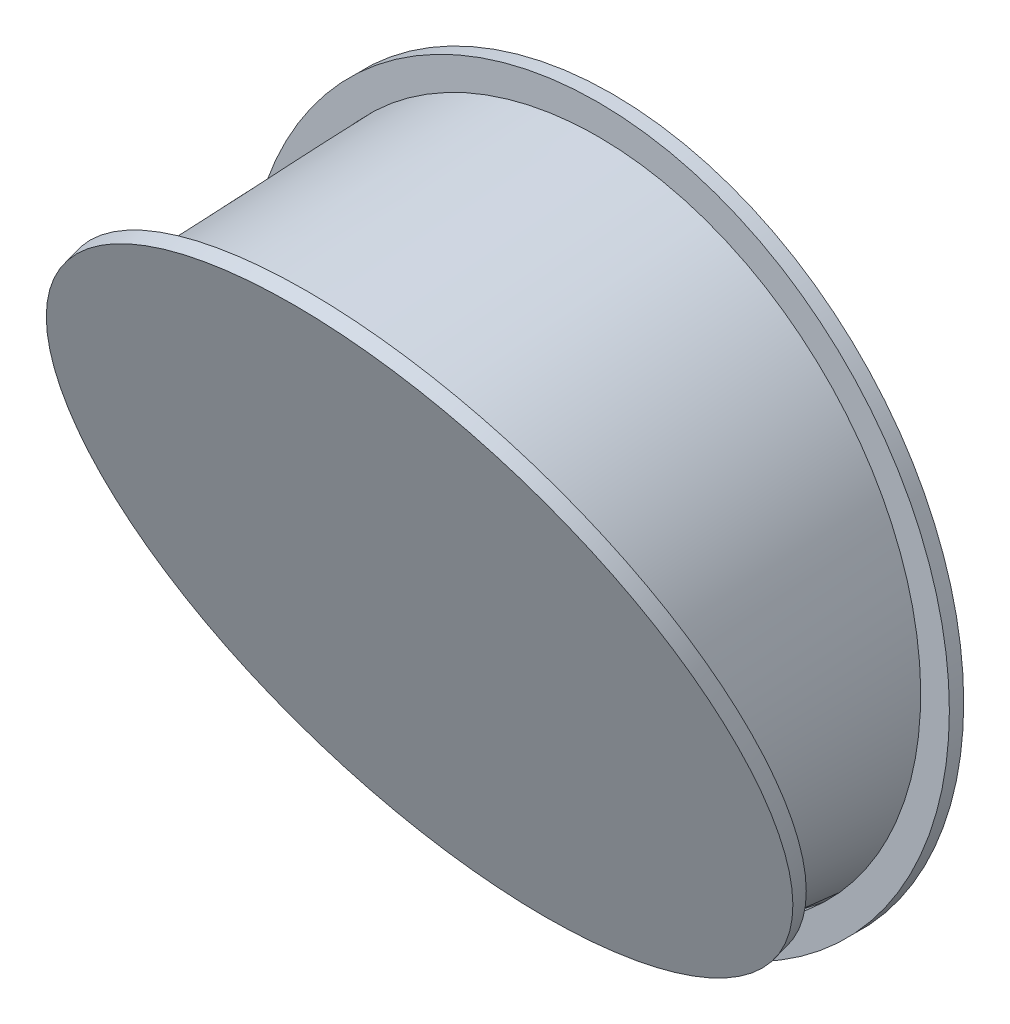
SolidWorks part; units mm, degrees
ref_plane "Front Plane" through (0, 0, 0) normal (0, 0, 1) x (1, 0, 0)
ref_plane "Top Plane" through (0, 0, 0) normal (0, 1, 0) x (1, 0, 0)
ref_plane "Right Plane" through (0, 0, 0) normal (1, 0, 0) x (0, 0, -1)
sketch "Sketch1" plane through (0, 0, 0) normal (0, 0, 1) x (1, 0, 0)
  line L0 (0, 34.9907) -> (0, -37.6588) construction
  line L1 (-13.89, -17.5) -> (14.3357, -17.5) construction
  circle A0 centre (0, 0) radius 11.25
  circle A1 centre (0, 0) radius 12.25
  point P8 (0, 11.25)
  dimension "D1" = 22.5
  dimension "D3" = 1
  dimension "D2" = 17.5
sketch "Sketch2" plane through (0, 0, 0) normal (1, 0, 0) x (0, 0, -1)
  line L0 (-19.9862, 0) -> (11.8569, 0) construction
ref_plane "Plane1" through (0, -2.2475, 5.8549) normal (0, -0.3584, 0.9336) x (1, 0, 0)
sketch "Sketch3" plane through (0, -2.2475, 5.8549) normal (0, -0.3584, 0.9336) x (1, 0, 0)
  line L2 (0, 19.9432) -> (0, -19.0864) construction
  circle A0 centre (0, 2.4074) radius 11.25
  circle A1 centre (0, 2.4074) radius 12.25
  point P4 (0, 13.6574)
  dimension "D1" = 22.5
  dimension "D2" = 1
loft "Loft1" add section "Sketch1" section "Sketch3" connector at (0.0572, 11.2499, 0) connector at (-0.0001, 10.5028, 10.7493)
extrude "Boss-Extrude1" add sketch "Sketch3<5>" against normal blind 0.5 contours A1
sketch "Sketch3<5>" plane through (0, -2.2475, 5.8549) normal (0, -0.3584, 0.9336) x (1, 0, 0) same geometry as "Sketch3"
extrude "Boss-Extrude2" add sketch "Sketch1<4>" along normal blind 0.5 contours A1
sketch "Sketch1<4>" plane through (0, 0, 0) normal (0, 0, 1) x (1, 0, 0) same geometry as "Sketch1"
